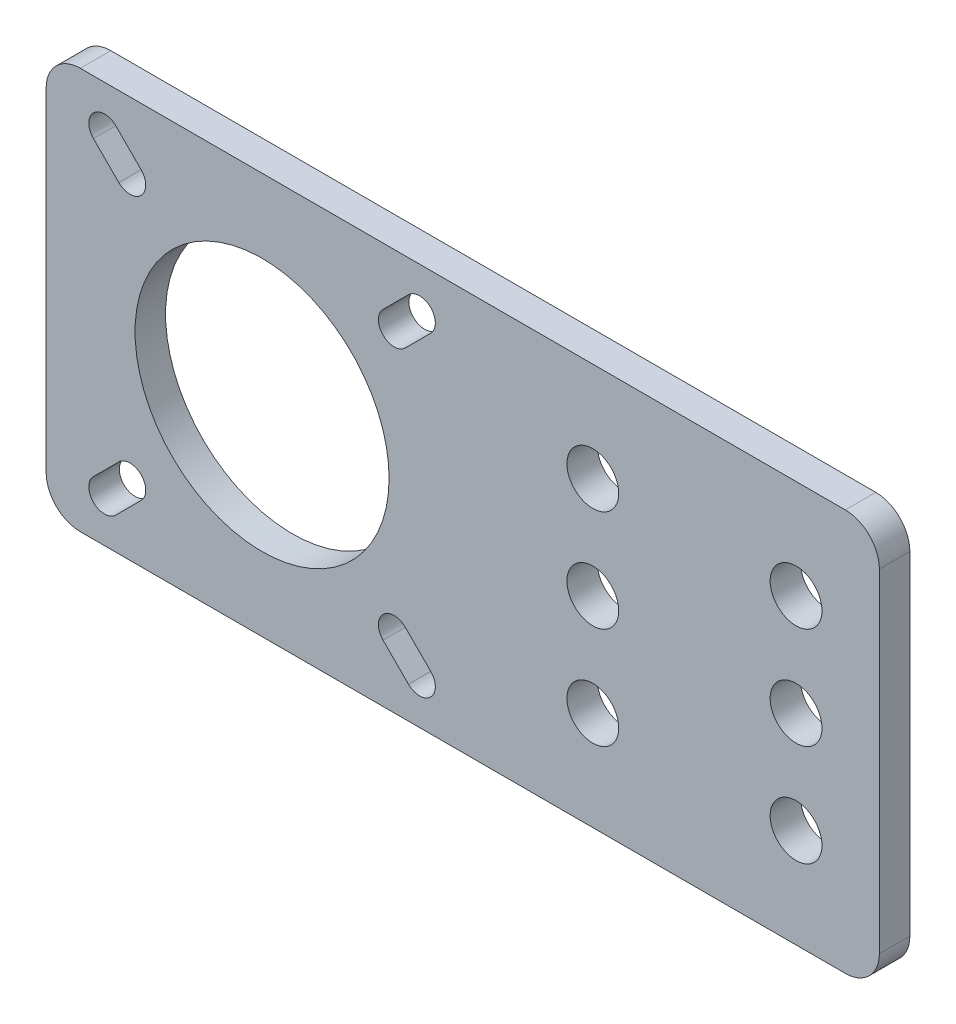
SolidWorks part; units mm, degrees
ref_plane "Plane1" through (0, 0, 0) normal (0, 0, 1) x (1, 0, 0)
ref_plane "Plane2" through (0, 0, 0) normal (0, 1, 0) x (1, 0, 0)
ref_plane "Plane3" through (0, 0, 0) normal (1, 0, 0) x (0, 0, -1)
sketch "Sketch1" plane through (0, 0, 0) normal (0, 0, 1) x (1, 0, 0)
  line L0 (-4.25, 15.5) -> (-6.75, 13) construction
  line L1 (-37.64, -19.75) -> (37.64, -19.75)
  line L2 (-41, -16.39) -> (-41, 16.39)
  line L3 (-37.64, 19.75) -> (37.64, 19.75)
  line L4 (41, -16.39) -> (41, 16.39)
  line L5 (-41, -19.75) -> (41, 19.75) construction
  line L6 (-41, 19.75) -> (41, -19.75) construction
  line L7 (-3.154, 14.404) -> (-5.654, 11.904)
  line L8 (-5.346, 16.596) -> (-7.846, 14.096)
  line L9 (-4.25, -15.5) -> (-6.75, -13) construction
  line L10 (-5.346, -16.596) -> (-7.846, -14.096)
  line L11 (-3.154, -14.404) -> (-5.654, -11.904)
  line L12 (-35.25, -15.5) -> (-32.75, -13) construction
  line L13 (-36.346, -14.404) -> (-33.846, -11.904)
  line L14 (-34.154, -16.596) -> (-31.654, -14.096)
  line L15 (0, 0) -> (12.8, 0) construction
  line L16 (12.8, 0) -> (12.8, 10) construction
  line L19 (-35.25, 15.5) -> (-32.75, 13) construction
  line L20 (-34.154, 16.596) -> (-31.654, 14.096)
  line L21 (-36.346, 14.404) -> (-33.846, 11.904)
  arc A0 (-37.64, -19.75) -> (-41, -16.39) centre (-37.64, -16.39) cw
  arc A1 (37.64, -19.75) -> (41, -16.39) centre (37.64, -16.39) ccw
  arc A2 (37.64, 19.75) -> (41, 16.39) centre (37.64, 16.39) cw
  arc A3 (-41, 16.39) -> (-37.64, 19.75) centre (-37.64, 16.39) cw
  circle A4 centre (-19.75, 0) radius 12.5
  arc A5 (-34.154, 16.596) -> (-36.346, 14.404) centre (-35.25, 15.5) ccw
  arc A6 (-33.846, 11.904) -> (-31.654, 14.096) centre (-32.75, 13) ccw
  arc A7 (-3.154, 14.404) -> (-5.346, 16.596) centre (-4.25, 15.5) ccw
  arc A8 (-7.846, 14.096) -> (-5.654, 11.904) centre (-6.75, 13) ccw
  arc A9 (-5.346, -16.596) -> (-3.154, -14.404) centre (-4.25, -15.5) ccw
  arc A10 (-5.654, -11.904) -> (-7.846, -14.096) centre (-6.75, -13) ccw
  arc A11 (-36.346, -14.404) -> (-34.154, -16.596) centre (-35.25, -15.5) ccw
  arc A12 (-31.654, -14.096) -> (-33.846, -11.904) centre (-32.75, -13) ccw
  circle A13 centre (12.8, 10) radius 2.55
  circle A14 centre (32.8, 10) radius 2.55
  circle A15 centre (12.8, 0) radius 2.55
  circle A16 centre (32.8, 0) radius 2.55
  circle A17 centre (12.8, -10) radius 2.55
  circle A18 centre (32.8, -10) radius 2.55
  point P0 (0, 0)
  point P25 (-5.5, 14.25)
  point P27 (-34, 14.25)
  point P38 (-5.5, -14.25)
  point P45 (-34, -14.25)
  dimension "D3" = 3.36
  dimension "D4" = 25
  dimension "D13" = 5.1
  dimension "D1" = 39.5
  dimension "D2" = 82
  dimension "D5" = 45
  dimension "D6" = 5.75
  dimension "D7" = 6.75
  dimension "D8" = 3.1
  dimension "D9" = 8.25
  dimension "D11" = 10
  dimension "D12" = 53.8
  dimension "D16" = 20
  dimension "D14" = 2
  dimension "D15" = 3
  dimension "D10" = 4
extrude "Extrude1" add sketch "Sketch1" along normal mid plane 3
ref_axis "Axis1" through (32.8, 10, 1.5) along (0, 0, -1)
ref_axis "Axis2" through (32.8, -10, 1.5) along (0, 0, -1)
ref_plane "Plane4" through (32.8, 0, 0) normal (-1, 0, 0) x (0, 0, 1)
